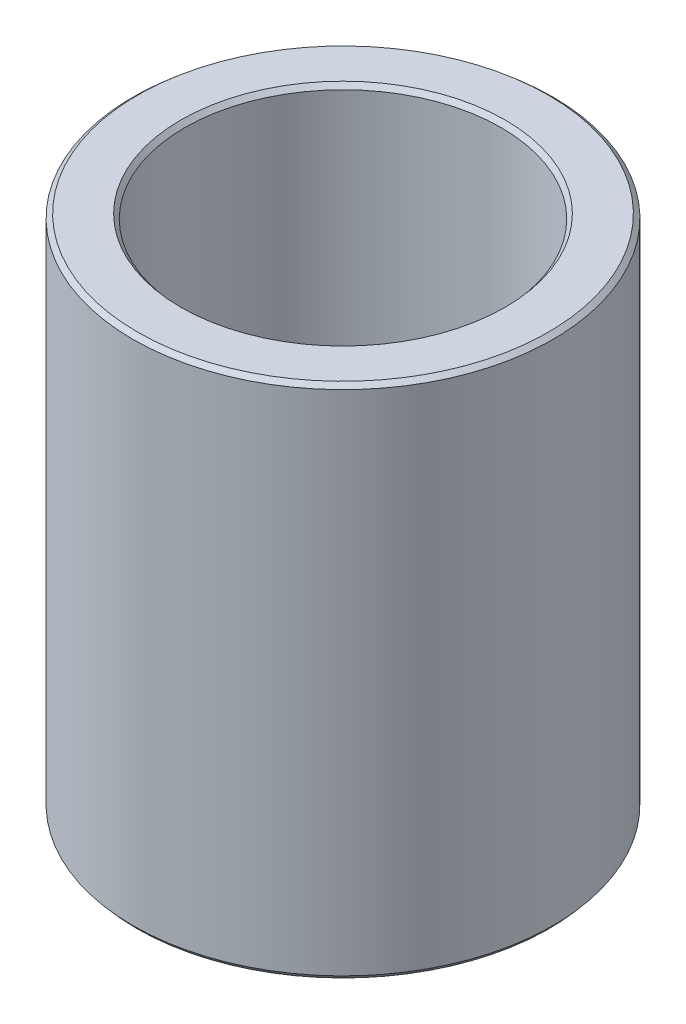
SolidWorks part; units mm, degrees
ref_plane "Front Plane" through (0, 0, 0) normal (0, 0, 1) x (1, 0, 0)
ref_plane "Top Plane" through (0, 0, 0) normal (0, 1, 0) x (1, 0, 0)
ref_plane "Right Plane" through (0, 0, 0) normal (1, 0, 0) x (0, 0, -1)
sketch "Sketch1" plane through (0, 0, 0) normal (0, 1, 0) x (1, 0, 0)
  circle A0 centre (0, 0) radius 42.5
  dimension "SLEEVE_OD" = 85
extrude "Boss-Extrude1" add sketch "Sketch1" along normal blind 104.5081
sketch "Sketch2" plane through (0, 0, 0) normal (0, 1, 0) x (1, 0, 0)
  circle A0 centre (0, 0) radius 32.0304
  dimension "BORE_D" = 64.0608
extrude "Cut-Extrude1" cut sketch "Sketch2" along normal through all
chamfer "Chamfer1" distance 0.8034 angle 49.335 4 edges at (0, 104.5081, 32.0304) (0, 0, 32.0304) (0, 0, 42.5) (0, 104.5081, 42.5) first distance on face at (0, 104.5081, 32.0304) first distance on face at (0, 0, 32.0304) first distance on face at (0, 104.5081, 42.5)
